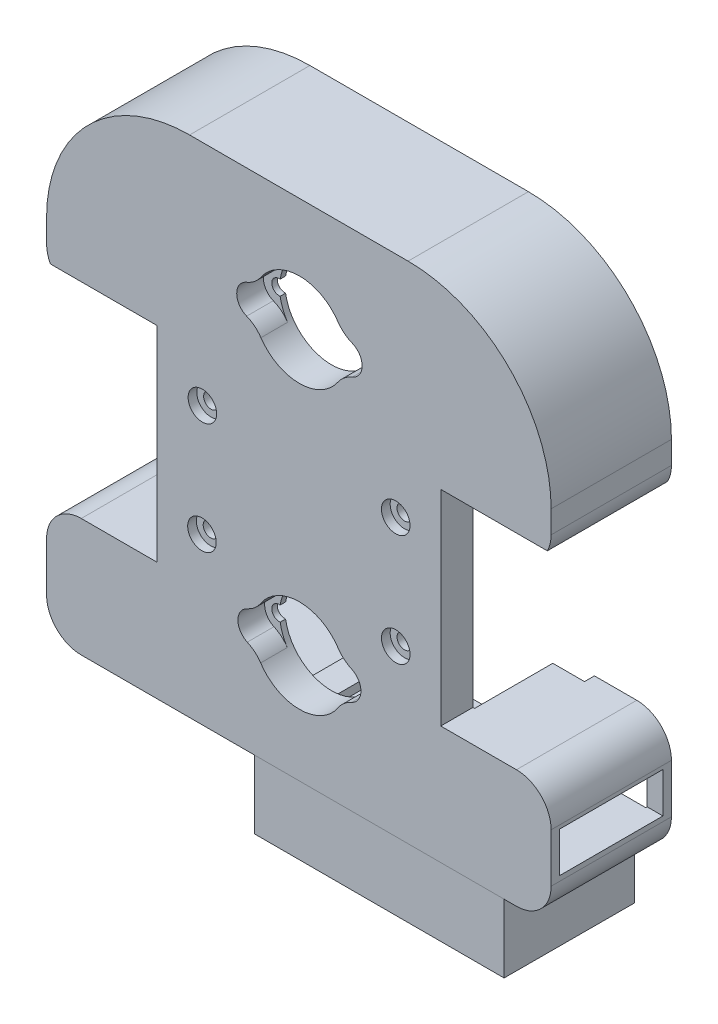
SolidWorks part; units mm, degrees
ref_plane "Front Plane" through (0, 0, 0) normal (0, 0, 1) x (1, 0, 0)
ref_plane "Top Plane" through (0, 0, 0) normal (0, 1, 0) x (1, 0, 0)
ref_plane "Right Plane" through (0, 0, 0) normal (1, 0, 0) x (0, 0, -1)
ref_plane "Plane1" through (0, 0, 2.54) normal (0, 0, 1) x (1, 0, 0)
sketch "Sketch1" plane through (0, 0, 2.54) normal (0, 0, 1) x (1, 0, 0)
  line L0 (-35.052, 0) -> (35.052, 0)
  line L1 (38.1, 3.048) -> (38.1, 10.922)
  line L2 (35.052, 13.97) -> (31.242, 13.97)
  line L3 (28.194, 17.018) -> (28.194, 45.974)
  line L4 (31.242, 49.022) -> (35.052, 49.022)
  line L5 (38.1, 52.07) -> (38.1, 55.7)
  line L6 (17.6, 76.2) -> (-17.6, 76.2)
  line L7 (-38.1, 55.7) -> (-38.1, 52.07)
  line L8 (-35.052, 49.022) -> (-31.242, 49.022)
  line L9 (-28.194, 45.974) -> (-28.194, 17.018)
  line L10 (-31.242, 13.97) -> (-35.052, 13.97)
  line L11 (-38.1, 10.922) -> (-38.1, 3.048)
  arc A0 (35.052, 49.022) -> (38.1, 52.07) centre (35.052, 52.07) ccw
  arc A1 (-38.1, 52.07) -> (-35.052, 49.022) centre (-35.052, 52.07) ccw
  arc A2 (-31.242, 49.022) -> (-28.194, 45.974) centre (-31.242, 45.974) cw
  arc A3 (28.194, 45.974) -> (31.242, 49.022) centre (31.242, 45.974) cw
  arc A4 (38.1, 10.922) -> (35.052, 13.97) centre (35.052, 10.922) ccw
  arc A5 (31.242, 13.97) -> (28.194, 17.018) centre (31.242, 17.018) cw
  arc A6 (-28.194, 17.018) -> (-31.242, 13.97) centre (-31.242, 17.018) cw
  arc A7 (-35.052, 13.97) -> (-38.1, 10.922) centre (-35.052, 10.922) ccw
  arc A8 (-35.052, 0) -> (-38.1, 3.048) centre (-35.052, 3.048) cw
  arc A9 (35.052, 0) -> (38.1, 3.048) centre (35.052, 3.048) ccw
  arc A10 (-17.6, 76.2) -> (-38.1, 55.7) centre (-17.6, 55.7) ccw
  arc A11 (38.1, 55.7) -> (17.6, 76.2) centre (17.6, 55.7) ccw
  dimension "D1" = 3.048
  dimension "D4" = 76.2
  dimension "D5" = 76.2
  dimension "D6" = 28.956
  dimension "D7" = 7.874
  dimension "D8" = 9.906
  dimension "D2" = 20.5
extrude "Boss-Extrude1" add sketch "Sketch1" against normal blind 17.78
sketch "Sketch2" plane through (0, 0, -15.24) normal (0, 0, -1) x (-1, 0, 0)
  line L12 (33.02, 54.102) -> (33.02, 55.7)
  line L13 (33.02, 54.102) -> (33.02, 55.7)
  line L14 (-33.02, 55.7) -> (-33.02, 54.102)
  line L15 (-33.02, 55.7) -> (-33.02, 54.102)
  line L24 (-33.02, 54.102) -> (-31.242, 54.102)
  line L25 (-23.114, 45.974) -> (-23.114, 17.018)
  line L26 (-31.242, 8.89) -> (-33.02, 8.89)
  line L27 (-33.02, 8.89) -> (-33.02, 5.08)
  line L28 (-33.02, 5.08) -> (33.02, 5.08)
  line L29 (33.02, 5.08) -> (33.02, 8.89)
  line L30 (33.02, 8.89) -> (31.242, 8.89)
  line L31 (23.114, 17.018) -> (23.114, 45.974)
  line L32 (31.242, 54.102) -> (33.02, 54.102)
  line L34 (17.6, 71.12) -> (-17.6, 71.12)
  line L36 (-33.02, 54.102) -> (-31.242, 54.102)
  line L37 (-23.114, 45.974) -> (-23.114, 17.018)
  line L38 (-31.242, 8.89) -> (-33.02, 8.89)
  line L39 (-33.02, 8.89) -> (-33.02, 5.08)
  line L40 (-33.02, 5.08) -> (33.02, 5.08)
  line L41 (33.02, 5.08) -> (33.02, 8.89)
  line L42 (33.02, 8.89) -> (31.242, 8.89)
  line L43 (23.114, 17.018) -> (23.114, 45.974)
  line L44 (31.242, 54.102) -> (33.02, 54.102)
  line L46 (17.6, 71.12) -> (-17.6, 71.12)
  arc A24 (-23.114, 45.974) -> (-31.242, 54.102) centre (-31.242, 45.974) ccw
  arc A25 (-31.242, 8.89) -> (-23.114, 17.018) centre (-31.242, 17.018) ccw
  arc A26 (23.114, 17.018) -> (31.242, 8.89) centre (31.242, 17.018) ccw
  arc A27 (31.242, 54.102) -> (23.114, 45.974) centre (31.242, 45.974) ccw
  arc A28 (33.02, 55.7) -> (17.6, 71.12) centre (17.6, 55.7) ccw
  arc A29 (-17.6, 71.12) -> (-33.02, 55.7) centre (-17.6, 55.7) ccw
  arc A30 (-23.114, 45.974) -> (-31.242, 54.102) centre (-31.242, 45.974) ccw
  arc A31 (-31.242, 8.89) -> (-23.114, 17.018) centre (-31.242, 17.018) ccw
  arc A32 (23.114, 17.018) -> (31.242, 8.89) centre (31.242, 17.018) ccw
  arc A33 (31.242, 54.102) -> (23.114, 45.974) centre (31.242, 45.974) ccw
  arc A34 (33.02, 55.7) -> (17.6, 71.12) centre (17.6, 55.7) ccw
  arc A35 (-17.6, 71.12) -> (-33.02, 55.7) centre (-17.6, 55.7) ccw
  dimension "D1" = 5.08
extrude "Cut-Extrude1" cut sketch "Sketch2" against normal blind 12.6
sketch "Sketch7" plane through (0, 0, -15.24) normal (0, 0, -1) x (-1, 0, 0)
  line L24 (-35.052, 46.482) -> (-31.242, 46.482)
  line L25 (-30.734, 45.974) -> (-30.734, 17.018)
  line L26 (-31.242, 16.51) -> (-35.052, 16.51)
  line L27 (-40.64, 10.922) -> (-40.64, 3.048)
  line L28 (-35.052, -2.54) -> (35.052, -2.54)
  line L29 (40.64, 3.048) -> (40.64, 10.922)
  line L30 (35.052, 16.51) -> (31.242, 16.51)
  line L31 (30.734, 17.018) -> (30.734, 45.974)
  line L32 (31.242, 46.482) -> (35.052, 46.482)
  line L33 (40.64, 52.07) -> (40.64, 55.7)
  line L34 (17.6, 78.74) -> (-17.6, 78.74)
  line L35 (-40.64, 55.7) -> (-40.64, 52.07)
  line L36 (-35.052, 46.482) -> (-31.242, 46.482)
  line L37 (-30.734, 45.974) -> (-30.734, 17.018)
  line L38 (-31.242, 16.51) -> (-35.052, 16.51)
  line L39 (-40.64, 10.922) -> (-40.64, 3.048)
  line L40 (-35.052, -2.54) -> (35.052, -2.54)
  line L41 (40.64, 3.048) -> (40.64, 10.922)
  line L42 (35.052, 16.51) -> (31.242, 16.51)
  line L43 (30.734, 17.018) -> (30.734, 45.974)
  line L44 (31.242, 46.482) -> (35.052, 46.482)
  line L45 (40.64, 52.07) -> (40.64, 55.7)
  line L46 (17.6, 78.74) -> (-17.6, 78.74)
  line L47 (-40.64, 55.7) -> (-40.64, 52.07)
  arc A12 (40.64, 55.7) -> (17.6, 78.74) centre (17.6, 55.7) ccw
  arc A13 (40.64, 55.7) -> (17.6, 78.74) centre (17.6, 55.7) ccw
  arc A18 (-17.6, 78.74) -> (-40.64, 55.7) centre (-17.6, 55.7) ccw
  arc A19 (-17.6, 78.74) -> (-40.64, 55.7) centre (-17.6, 55.7) ccw
  arc A24 (-40.64, 52.07) -> (-35.052, 46.482) centre (-35.052, 52.07) ccw
  arc A25 (-30.734, 45.974) -> (-31.242, 46.482) centre (-31.242, 45.974) ccw
  arc A26 (-31.242, 16.51) -> (-30.734, 17.018) centre (-31.242, 17.018) ccw
  arc A27 (-35.052, 16.51) -> (-40.64, 10.922) centre (-35.052, 10.922) ccw
  arc A28 (-40.64, 3.048) -> (-35.052, -2.54) centre (-35.052, 3.048) ccw
  arc A29 (35.052, -2.54) -> (40.64, 3.048) centre (35.052, 3.048) ccw
  arc A30 (40.64, 10.922) -> (35.052, 16.51) centre (35.052, 10.922) ccw
  arc A31 (30.734, 17.018) -> (31.242, 16.51) centre (31.242, 17.018) ccw
  arc A32 (31.242, 46.482) -> (30.734, 45.974) centre (31.242, 45.974) ccw
  arc A33 (35.052, 46.482) -> (40.64, 52.07) centre (35.052, 52.07) ccw
  arc A36 (-40.64, 52.07) -> (-35.052, 46.482) centre (-35.052, 52.07) ccw
  arc A37 (-30.734, 45.974) -> (-31.242, 46.482) centre (-31.242, 45.974) ccw
  arc A38 (-31.242, 16.51) -> (-30.734, 17.018) centre (-31.242, 17.018) ccw
  arc A39 (-35.052, 16.51) -> (-40.64, 10.922) centre (-35.052, 10.922) ccw
  arc A40 (-40.64, 3.048) -> (-35.052, -2.54) centre (-35.052, 3.048) ccw
  arc A41 (35.052, -2.54) -> (40.64, 3.048) centre (35.052, 3.048) ccw
  arc A42 (40.64, 10.922) -> (35.052, 16.51) centre (35.052, 10.922) ccw
  arc A43 (30.734, 17.018) -> (31.242, 16.51) centre (31.242, 17.018) ccw
  arc A44 (31.242, 46.482) -> (30.734, 45.974) centre (31.242, 45.974) ccw
  arc A45 (35.052, 46.482) -> (40.64, 52.07) centre (35.052, 52.07) ccw
  arc M47 (-38.1, 52.07) -> (-35.052, 49.022) centre (-35.052, 52.07) ccw
  line M48 (-35.052, 49.022) -> (-31.242, 49.022)
  arc M49 (-31.242, 49.022) -> (-28.194, 45.974) centre (-31.242, 45.974) cw
  line M50 (-28.194, 45.974) -> (-28.194, 17.018)
  arc M51 (-28.194, 17.018) -> (-31.242, 13.97) centre (-31.242, 17.018) cw
  line M52 (-31.242, 13.97) -> (-35.052, 13.97)
  arc M53 (-35.052, 13.97) -> (-38.1, 10.922) centre (-35.052, 10.922) ccw
  line M54 (-38.1, 10.922) -> (-38.1, 3.048)
  arc M55 (-38.1, 3.048) -> (-35.052, 0) centre (-35.052, 3.048) ccw
  line M56 (-35.052, 0) -> (35.052, 0)
  arc M57 (35.052, 0) -> (38.1, 3.048) centre (35.052, 3.048) ccw
  line M58 (38.1, 3.048) -> (38.1, 10.922)
  arc M59 (38.1, 10.922) -> (35.052, 13.97) centre (35.052, 10.922) ccw
  line M60 (35.052, 13.97) -> (31.242, 13.97)
  arc M61 (31.242, 13.97) -> (28.194, 17.018) centre (31.242, 17.018) cw
  line M62 (28.194, 17.018) -> (28.194, 45.974)
  arc M63 (28.194, 45.974) -> (31.242, 49.022) centre (31.242, 45.974) cw
  line M64 (31.242, 49.022) -> (35.052, 49.022)
  arc M65 (35.052, 49.022) -> (38.1, 52.07) centre (35.052, 52.07) ccw
  line M66 (38.1, 52.07) -> (38.1, 55.7)
  arc M67 (38.1, 55.7) -> (17.6, 76.2) centre (17.6, 55.7) ccw
  line M68 (17.6, 76.2) -> (-17.6, 76.2)
  arc M69 (-17.6, 76.2) -> (-38.1, 55.7) centre (-17.6, 55.7) ccw
  line M70 (-38.1, 55.7) -> (-38.1, 52.07)
  dimension "D1" = 2.54
extrude "Boss-Extrude2" add sketch "Sketch7" along normal blind 1.6 and the other way up to surface (17.78 mm away) contours L46 A19 L47 A36 L36 A37 L37 A38 L38 A39 L39 A40 L40 A41 L41 A42 L42 A43 L43 A44 L44 A45 L45 A13 M47 M70 M69 M68 M67 M66 M65 M64 M63 M62 M61 M60 M59 M58 M57 M56 M55 M54 M53 M52 M51 M50 M49 M48 region at (38.1905, 48.9315, -15.24) other way up to face at (0, 32.5442, 2.54)
sketch "Sketch8" plane through (0, 0, -16.84) normal (0, 0, -1) x (-1, 0, 0)
  line L9 (-22.86, 49.53) -> (-22.86, 16.51)
  line L18 (-22.86, 49.53) -> (-46.482, 49.53)
  line L19 (-46.482, 49.53) -> (-46.482, 16.51)
  line L20 (-46.482, 16.51) -> (-22.86, 16.51)
  line L27 (0, 55) -> (0, -55) construction
  line L28 (46.482, 16.51) -> (22.86, 16.51)
  line L30 (22.86, 49.53) -> (22.86, 16.51)
  line L31 (22.86, 49.53) -> (46.482, 49.53)
  line L32 (46.482, 49.53) -> (46.482, 16.51)
  line L33 (-38.1, 10.922) -> (-38.1, 3.048) construction
  line L34 (-35.052, 0) -> (35.052, 0) construction
  dimension "D1" = 23.622
  dimension "D2" = 33.02
  dimension "D3" = 15.24
  dimension "D4" = 16.51
extrude "Cut-Extrude2" cut sketch "Sketch8" against normal up to surface (19.38 mm away) up to face at (0, 32.5442, 2.54)
sketch "Sketch10" plane through (0, 0, 2.54) normal (0, 0, 1) x (1, 0, 0)
  line L0 (-7.62, 39.878) -> (7.62, 39.878)
  line L1 (7.62, 39.878) -> (7.62, 27.178)
  line L2 (7.62, 27.178) -> (-7.62, 27.178)
  line L3 (-7.62, 27.178) -> (-7.62, 39.878)
  line L4 (-22.86, 49.53) -> (-22.86, 16.51) construction
  dimension "D1" = 12.7
  dimension "D2" = 15.24
  dimension "D3" = 27.178
  dimension "D4" = 15.24
sketch "Sketch16" plane through (0, 0, -15.24) normal (0, 0, -1) x (-1, 0, 0)
  line L0 (-17.6, 71.12) -> (-17.6, 69.4347)
  line L1 (17.6, 71.12) -> (17.6, 69.4347)
  line L2 (17.6, 69.4347) -> (-17.6, 69.4347)
  line L3 (0, 5.08) -> (0, 6.4137)
  line L4 (-33.02, 5.08) -> (33.02, 5.08) construction
  line L5 (0, 6.4137) -> (4.6024, 6.4137)
  line L6 (4.6024, 6.4137) -> (4.6024, 5.08)
  line L7 (-33.02, 5.08) -> (33.02, 5.08) construction
  line L8 (-17.6, 71.12) -> (17.6, 71.12)
  line L9 (0, 5.08) -> (4.6024, 5.08)
extrude "Boss-Extrude4" add sketch "Sketch16" against normal blind 12.5
sketch "Sketch15" plane through (0, 0, -15.24) normal (0, 0, -1) x (-1, 0, 0)
  circle A0 centre (-14.3428, 72.1225) radius 1.6002
  circle A1 centre (16.2191, 72.2313) radius 1.6002
  circle A2 centre (2.364, 4.3291) radius 1.6002
extrude "Cut-Extrude5" cut sketch "Sketch15" against normal blind 14
sketch "Sketch18" plane through (0, 0, 2.54) normal (0, 0, 1) x (1, 0, 0)
  line L0 (-7.4574, 60.4219) -> (7.6426, 60.4219) construction
  line L1 (-7.4574, 78.74) -> (-7.4574, -2.54) construction
  line L2 (-17.6, 78.74) -> (17.6, 78.74) construction
  line L3 (35.052, -2.54) -> (-35.052, -2.54) construction
  line L4 (7.6426, 78.74) -> (7.6426, -2.54) construction
  circle A0 centre (-15.5415, 42.0064) radius 1.2
  circle A1 centre (15.61, 42.0064) radius 1.2
  circle A2 centre (15.61, 24.02) radius 1.2
  circle A4 centre (-15.61, 24.02) radius 1.2
  circle A5 centre (-7.4574, 60.4219) radius 1.2
  circle A6 centre (7.6426, 60.4219) radius 1.2
  circle A7 centre (7.4473, 14.9571) radius 1.2
  circle A8 centre (-7.4574, 14.9571) radius 1.2
  point P10 (0.0926, 60.4219)
  dimension "D1" = 15.1
  dimension "D2" = 7.55
  dimension "D3" = 7.55
extrude "Cut-Extrude6" cut sketch "Sketch18" against normal through all both and the other way through all
sketch "Sketch21" plane through (0, 0, -2.64) normal (0, 0, -1) x (-1, 0, 0)
  circle A0 centre (-15.61, 42.0064) radius 2.3
  circle A1 centre (-15.61, 24.02) radius 2.3
  circle A3 centre (15.5415, 42.0064) radius 2.3
  circle A4 centre (15.61, 24.02) radius 2.3
sketch "Sketch37" plane through (0, -2.54, 0) normal (0, -1, 0) x (1, 0, 0)
  line L4 (-7.1274, 2.54) -> (-7.1274, -18.46)
  line L5 (-7.1274, -18.46) -> (33.1008, -18.46)
  line L6 (33.1008, -18.46) -> (33.0644, 2.54)
  line L7 (33.0644, 2.54) -> (-7.1274, 2.54)
extrude "Boss-Extrude9" add sketch "Sketch37" along normal blind 11 separate body
sketch "Sketch40" plane through (0, 0, -18.46) normal (0, 0, -1) x (-1, 0, 0)
  line L0 (-30.4986, -1.2515) -> (-30.4986, -12.0948)
  line L1 (-30.4986, -12.0948) -> (5.0014, -12.0948)
  line L2 (5.0014, -12.0948) -> (5.0014, -1.2515)
  line L8 (5.0014, -1.2515) -> (-30.4986, -1.2515)
  dimension "D2" = 35.5
extrude "Cut-Extrude14" cut sketch "Sketch40" against normal blind 20.5
sketch "Sketch41" plane through (0, 0, 2.54) normal (0, 0, 1) x (1, 0, 0)
  circle A0 centre (-15.5415, 42.0064) radius 2.3
  circle A1 centre (15.61, 42.0064) radius 2.3
  circle A2 centre (-15.61, 24.02) radius 2.3
  circle A3 centre (15.61, 24.02) radius 2.3
extrude "Cut-Extrude15" cut sketch "Sketch41" against normal blind 1.4
sketch "Sketch43" plane through (0, 0, 2.54) normal (0, 0, 1) x (1, 0, 0)
  line L0 (-7.4574, 60.4219) -> (7.6426, 60.4219) construction
  line L1 (0, 78.74) -> (0, -2.54) construction
  line L2 (-17.6, 78.74) -> (17.6, 78.74) construction
  line L3 (35.052, -2.54) -> (-35.052, -2.54) construction
  line L4 (-7.2621, 14.9571) -> (7.4473, 14.9571) construction
  line L5 (-7.7532, 78.74) -> (-7.1274, -2.54) construction
  line L6 (7.5926, 78.74) -> (7.5926, -2.54) construction
  circle A0 centre (0.0926, 60.4219) radius 7.5
  circle A1 centre (-7.4574, 60.4219) radius 2.55
  circle A2 centre (7.6426, 60.4219) radius 2.55
  circle A3 centre (0.0926, 14.9571) radius 7.5
  circle A5 centre (-7.2621, 14.9571) radius 2.55
  circle A6 centre (7.4473, 14.9571) radius 2.55
  point P21 (0, 0)
  point P25 (0, 0)
  point P27 (0, 0)
  point P29 (7.4473, 14.9571)
  point P30 (0, 0)
  circle M9 centre (-7.4574, 60.4219) radius 1.2
  circle M10 centre (7.6426, 60.4219) radius 1.2
  circle M34 centre (-7.4574, 14.9571) radius 1.2
  circle M35 centre (7.4473, 14.9571) radius 1.2
  dimension "D1" = 15
  dimension "D2" = 5.1
  dimension "D3" = 5.1
extrude "Cut-Extrude16" cut sketch "Sketch43" against normal blind 11 contours A6 A3 A5 | A3 A6 M35 | A3 A5 M34 | A0 region at (6.1607, 14.9571, 2.54) region at (0.0926, 14.9571, 2.54) region at (-6.0008, 14.9571, 2.54)
sketch "Sketch44" plane through (-40.64, 0, 0) normal (-1, 0, 0) x (0, 0, 1)
  line L0 (-15.3525, 10.3016) -> (-15.3525, 3.9635)
  line L1 (-15.3525, 3.9635) -> (1.4992, 3.9635)
  line L2 (1.4992, 3.9635) -> (1.4992, 10.3016)
  line L3 (1.4992, 10.3016) -> (-15.3525, 10.3016)
extrude "Cut-Extrude17" cut sketch "Sketch44" against normal blind 10
sketch "Sketch45" plane through (40.64, 0, 0) normal (1, 0, 0) x (0, 0, -1)
  line L0 (15.4685, 3.8487) -> (15.4685, 10.335)
  line L1 (15.4685, 10.335) -> (-1.1525, 10.335)
  line L2 (-1.1525, 10.335) -> (-1.1525, 3.8487)
  line L3 (-1.1525, 3.8487) -> (15.4685, 3.8487)
extrude "Cut-Extrude18" cut sketch "Sketch45" against normal blind 10
extrude "Cut-Extrude19" cut sketch "Sketch43<4>" against normal blind 4.3 contours A3 A6 M35 | A3 A5 M34 | A0 A1 M9 | A0 A2 M10 region at (7.417, 62.2919, 2.54) region at (-7.2318, 62.2919, 2.54) region at (7.4113, 16.8455, 2.54) region at (-7.2271, 16.8417, 2.54)
sketch "Sketch43<4>" plane through (0, 0, 2.54) normal (0, 0, 1) x (1, 0, 0) same geometry as "Sketch43"
fillet "Fillet1" radius 5.08 2 edges at (-6.9668, 12.4243, 0.39) (-6.9668, 17.4899, 0.39)
fillet "Fillet2" radius 5.08 2 edges at (7.152, 12.4243, 0.39) (7.152, 17.4899, 0.39)
fillet "Fillet4" radius 5.08 4 edges at (7.1621, 62.9263, 0.39) (7.1621, 57.9176, 0.39) (-6.9769, 62.9263, 0.39) (-6.9769, 57.9176, 0.39)
